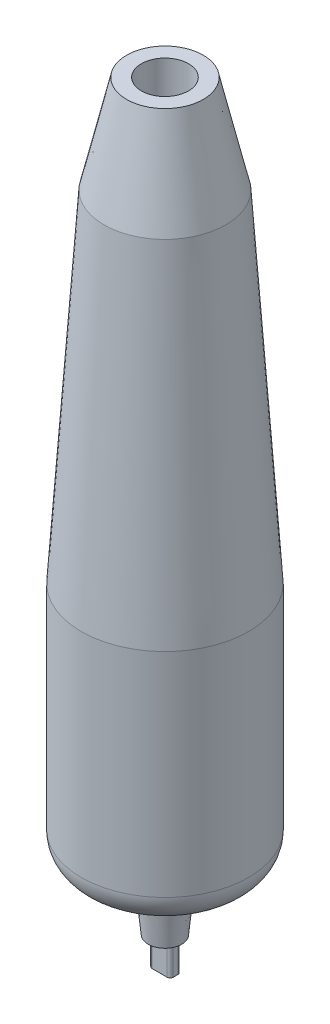
SolidWorks part; units mm, degrees
ref_plane "Front Plane" through (0, 0, 0) normal (0, 0, 1) x (1, 0, 0)
ref_plane "Top Plane" through (0, 0, 0) normal (0, 1, 0) x (1, 0, 0)
ref_plane "Right Plane" through (0, 0, 0) normal (1, 0, 0) x (0, 0, -1)
sketch "Sketch2" plane through (0, 0, 0) normal (0, 0, 1) x (1, 0, 0)
  line L0 (0, 0) -> (5.5, 0)
  line L1 (5.5, 0) -> (7.5, 20)
  line L2 (7.5, 20) -> (27.5, 20)
  line L3 (27.5, 20) -> (27.5, 100)
  line L4 (27.5, 100) -> (20, 212)
  line L5 (20, 212) -> (12.6, 244)
  line L6 (12.6, 244) -> (7.75, 244)
  line L7 (7.75, 244) -> (7.75, 229)
  line L8 (7.75, 229) -> (0, 229)
  line L9 (0, 229) -> (0, 0)
  dimension "D1" = 5.5
  dimension "D2" = 20
  dimension "D3" = 27.5
  dimension "D4" = 7.5
  dimension "D5" = 100
  dimension "D6" = 212
  dimension "D7" = 20
  dimension "D8" = 32
  dimension "D9" = 12.6
  dimension "D10" = 15
  dimension "D11" = 7.75
revolve "Revolve1" add sketch "Sketch2" angle 360 about L9
fillet "Fillet1" radius 10 1 edges at (0, 20, 27.5)
sketch "Sketch3" plane through (0, 0, 0) normal (0, -1, 0) x (1, 0, 0)
  line L1 (-3.5, -1.775) -> (3.5, -1.775)
  line L2 (-3.5, -1.775) -> (-3.5, 1.775)
  line L3 (-3.5, 1.775) -> (3.5, 1.775)
  line L4 (3.5, -1.775) -> (3.5, 1.775)
  line L5 (-3.5, -1.775) -> (3.5, 1.775) construction
  line L6 (-3.5, 1.775) -> (3.5, -1.775) construction
  point P0 (0, 0)
  point P8 (0, 0)
  dimension "D1" = 3.55
  dimension "D2" = 7
extrude "Boss-Extrude2" add sketch "Sketch3" along normal blind 10
fillet "Fillet2" radius 1 9 edges at (3.5, 0, 0) (0, 0, 1.775) (0, 0, -1.775) (-3.5, -5, 1.775) (-3.5, -10, 0) (-3.5, -5, -1.775) (-3.5, 0, 0) (3.5, -5, -1.775) (3.5, -5, 1.775)
